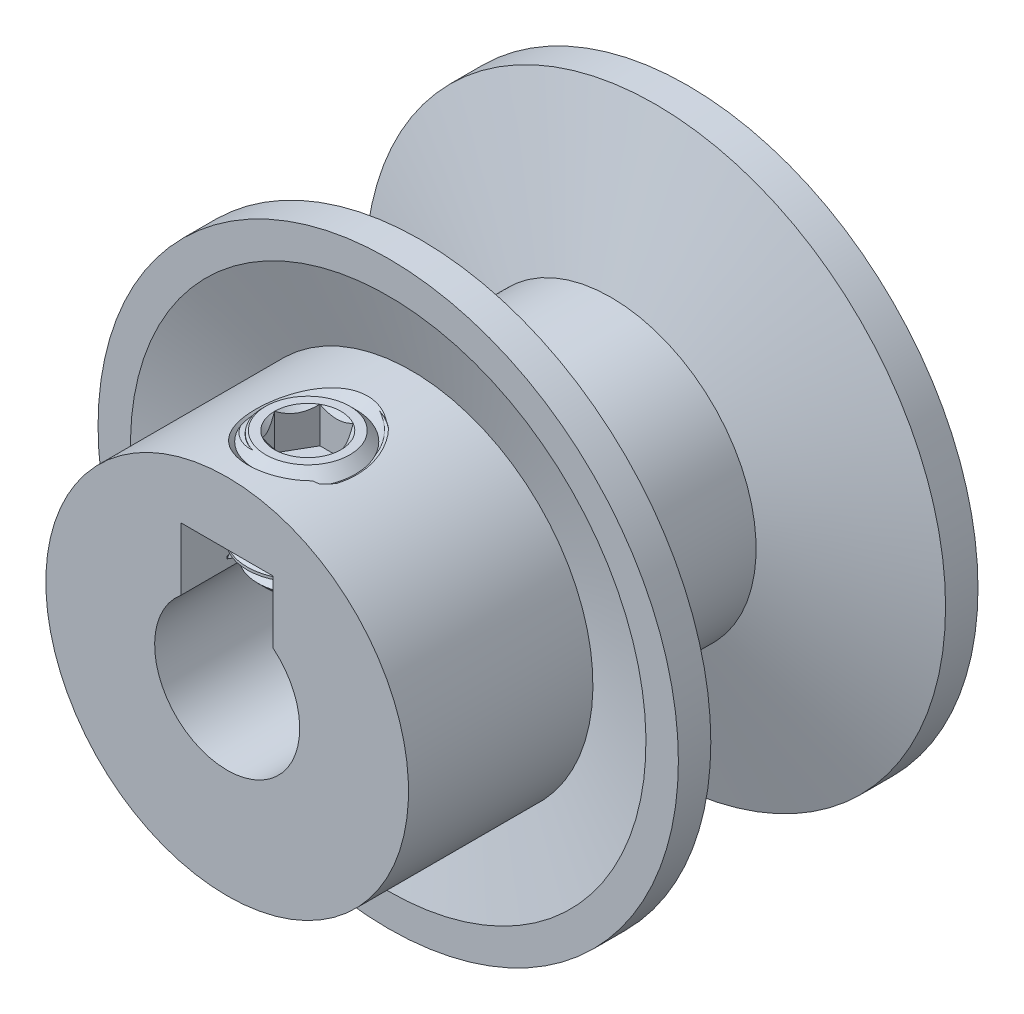
SolidWorks part; units mm, degrees
ref_plane "Front Plane" through (0, 0, 0) normal (0, 0, 1) x (1, 0, 0)
ref_plane "Top Plane" through (0, 0, 0) normal (0, 1, 0) x (1, 0, 0)
ref_plane "Right Plane" through (0, 0, 0) normal (1, 0, 0) x (0, 0, -1)
sketch "Sketch1" plane through (0, 0, 0) normal (1, 0, 0) x (0, 0, -1)
  line L0 (-21.4249, 0) -> (10.3251, 0) construction
  line L1 (-8.0899, 20) -> (8.0899, 20) construction
  line L2 (8.0899, 20) -> (10.3251, 20)
  line L5 (-10.3251, 20) -> (10.3251, 20) construction
  line L7 (-10.3251, 0) -> (-10.3251, 12.5)
  line L9 (-10.3251, 17.7648) -> (-8.7155, 12.5)
  line L13 (-8.0899, 20) -> (-5.0326, 10)
  line L14 (-5.0326, 10) -> (5.0326, 10)
  line L15 (5.0326, 10) -> (8.0899, 20)
  line L16 (10.3251, 5) -> (-21.4249, 5) construction
  line L17 (0, 20) -> (0, 0) construction
  line L18 (-8.0899, 20) -> (-10.3251, 20)
  line L20 (-21.4249, 0) -> (-21.4249, 5) construction
  line L22 (5.109, 10.25) -> (-5.109, 10.25) construction
  line L23 (10.3251, 20) -> (10.3251, 0) construction
  line L24 (-8.7155, 12.5) -> (-10.3251, 12.5)
  line L26 (-10.3251, 0) -> (6.3564, 0)
  line L27 (6.3564, 6.15) -> (6.7741, 6.15)
  line L28 (6.7741, 6.15) -> (10.3251, 17.7648)
  line L29 (-10.3251, 17.7648) -> (-10.3251, 20)
  line L31 (10.3251, 17.7648) -> (10.3251, 20)
  line L32 (6.3564, 0) -> (6.3564, 6.15)
  line L33 (10.3251, 20) -> (10.3251, 0) construction
  line L34 (-21.4249, 12.5) -> (-21.4249, -12.5) construction
  line L35 (5.8581, 12.7) -> (-5.8581, 12.7) construction
  point P16 (0, 10)
  point P38 (-10.3124, 0)
revolve "Revolve1" add sketch "Sketch1" angle 360 about L0
sketch "Sketch2" plane through (0, 0, 0) normal (1, 0, 0) x (0, 0, -1)
  line L0 (10.3251, 0) -> (-21.4249, 0) construction
  line L3 (-10.3124, 0) -> (-10.3124, 12.5)
  line L4 (-10.3124, 12.5) -> (-21.4249, 12.5)
  line L5 (-21.4249, 12.5) -> (-21.4249, 0)
  line L8 (-21.4249, 0) -> (-10.3124, 0)
revolve "Revolve2" add sketch "Sketch2" angle 360 about L0
sketch "Sketch3" plane through (0, 0, 21.4249) normal (0, 0, -1) x (-1, 0, 0)
  line L0 (-3.175, 5) -> (3.175, 5) construction
  line L1 (-3.175, 8.175) -> (3.175, 8.175) construction
  line L2 (-3.175, 8.175) -> (-3.175, 1.825) construction
  line L3 (-3.175, 1.825) -> (3.175, 1.825) construction
  line L4 (3.175, 8.175) -> (3.175, 1.825) construction
  circle A0 centre (0, 0) radius 5
  circle A1 centre (0, 0) radius 10.25 construction
  circle A2 centre (0, 0) radius 12.7 construction
  dimension "Keyway Wd." = 6.35
  dimension "Keyway Dp." = 3.175
extrude "Cut-Extrude1" cut sketch "Sketch3" along normal up to vertex (31.75 mm away) up to point (0, 0, -10.3251)
sketch "Sketch4" plane through (0, 0, 21.4249) normal (0, 0, -1) x (-1, 0, 0)
  line L0 (-3.175, 8.175) -> (-3.175, 1.825) construction
  line L1 (-3.175, 8.175) -> (3.175, 8.175) construction
  line L2 (3.175, 8.175) -> (3.175, 1.825) construction
  line L3 (-3.175, 1.825) -> (3.175, 1.825) construction
  line L4 (-3.175, 8.175) -> (-3.175, 1.825)
  line L5 (-3.175, 8.175) -> (3.175, 8.175)
  line L6 (3.175, 8.175) -> (3.175, 1.825)
  line L7 (-3.175, 1.825) -> (3.175, 1.825)
  line L8 (-3.175, 5) -> (3.175, 5) construction
  line L9 (-3.175, 5) -> (3.175, 5) construction
extrude "Cut-Extrude2" cut sketch "Sketch4" along normal up to vertex (31.75 mm away) up to point (0, 0, -10.3251)
ref_plane "Plane1" through (0, 12.5, 0) normal (0, 1, 0) x (-1, 0, 0)
sketch "Sketch5" plane through (0, 12.5, 0) normal (0, 1, 0) x (-1, 0, 0)
  line L0 (0, 10.3124) -> (0, 21.4249) construction
  line L7 (0, 19.8374) -> (0, 18.4263) construction
  circle A0 centre (0, 15.8686) radius 3.9688 construction
  circle A1 centre (0, 15.8686) radius 3.0868
  dimension "D3" = 0.8819
extrude "Cut-Extrude3" cut sketch "Sketch5" against normal up to surface (12.5 mm away) up to plane "Top Plane"
sketch "Sketch6" plane through (0, 12.5, 0) normal (0, 1, 0) x (-1, 0, 0)
  circle A0 centre (0, 15.8686) radius 3.9688 construction
  circle A1 centre (0, 15.8686) radius 3.9688
  point P3 (0, 19.8374)
curve "Helix/Spiral1" pitch 1.4111 height 13.9111 radius 3.9688 centre (0, 12.5, 15.8686) axis (0, -1, 0) start towards (0, 0, 1)
sketch "Sketch7" plane through (0, 0, 0) normal (1, 0, 0) x (0, 0, -1)
  line L0 (-18.7681, 13.9111) -> (-18.7681, 12.5) construction
  line L1 (-18.7681, 12.5) -> (-19.9902, 13.2056) construction
  line L2 (-19.9902, 13.2056) -> (-18.7681, 13.9111) construction
  line L3 (-18.7681, 12.5) -> (-19.8374, 12.5) construction
  line L4 (-19.8374, 12.5) -> (-19.8374, 13.1174) construction
  line L5 (-19.8374, 13.1174) -> (-19.8374, 13.2937) construction
  line L6 (-18.9209, 12.5882) -> (-18.9209, 13.8229) construction
  line L7 (-19.9902, 13.2056) -> (-19.8374, 13.2056) construction
  line L8 (-18.9209, 13.2056) -> (-18.7681, 13.2056) construction
  line L9 (-18.8445, 13.867) -> (-18.8445, 12.5441)
  line L10 (-18.8445, 12.5441) -> (-19.8374, 13.1174)
  line L11 (-19.8374, 13.1174) -> (-19.8374, 13.2937)
  line L12 (-19.8374, 13.2937) -> (-18.8445, 13.867)
  point P16 (-18.8445, 13.2056)
  dimension "D1" = 1.4111
  dimension "D2" = 0.1764
sweep "Cut-Sweep1" cut profiles "Sketch7" path "Helix/Spiral1" align with end faces yes
sketch "Sketch8" plane through (0, 12.5, 0) normal (0, 1, 0) x (-1, 0, 0)
  circle A0 centre (0, 15.8686) radius 4.1215
extrude "Cut-Extrude4" cut sketch "Sketch8" against normal through all draft 45
sketch "Sketch9" plane through (0, 0, 0) normal (1, 0, 0) x (0, 0, -1)
  line L0 (-15.8686, 12.5) -> (-15.8686, 4.5625) construction
  line L1 (-19.8374, 5.6318) -> (-19.8374, 11.4307)
  line L2 (-15.8686, 12.5) -> (-19.8374, 12.5) construction
  line L3 (-15.8686, 12.5) -> (-15.8686, 4.5625)
  line L4 (-15.8686, 4.5625) -> (-19.8374, 4.5625) construction
  line L5 (-19.8374, 12.5) -> (-19.8374, 4.5625) construction
  line L6 (-18.7681, 12.5) -> (-19.8374, 11.4307)
  line L7 (-19.8374, 5.6318) -> (-18.7681, 4.5625)
  line L8 (-18.7681, 12.5) -> (-15.8686, 12.5)
  line L9 (-18.7681, 4.5625) -> (-15.8686, 4.5625)
  line L10 (-10.3124, 12.5) -> (-21.4249, 12.5) construction
  line L11 (-18.7681, 12.5) -> (-19.8374, 12.5) construction
  line L12 (-19.8374, 12.5) -> (-19.8374, 11.4307) construction
revolve "Revolve3" add sketch "Sketch9" angle 360 about L0
sketch "Sketch10" plane through (0, 12.5, 0) normal (0, 1, 0) x (-1, 0, 0)
  circle A1 centre (0, 15.8686) radius 3.9688
  circle A2 centre (0, 15.8686) radius 3.9688
  dimension "D1" = 0
curve "Helix/Spiral2" pitch 1.4111 height 9.3486 turns 6.625
sketch "Sketch11" plane through (0, 0, 0) normal (1, 0, 0) x (0, 0, -1)
  line L0 (-19.9902, 13.2056) -> (-19.9902, 11.7944) construction
  line L1 (-19.9902, 11.7944) -> (-18.7681, 12.5) construction
  line L2 (-18.7681, 12.5) -> (-19.9902, 13.2056) construction
  line L4 (-18.9209, 12.5882) -> (-18.9209, 12.4118)
  line L5 (-18.9209, 12.4118) -> (-19.8374, 11.8826)
  line L6 (-19.8374, 11.8826) -> (-19.8374, 13.1174)
  line L7 (-19.8374, 13.1174) -> (-18.9209, 12.5882)
sweep "Cut-Sweep2" cut profiles "Sketch11" path "Helix/Spiral2" align with end faces yes
sketch "Sketch12" plane through (0, 12.5, 0) normal (0, 1, 0) x (1, 0, 0)
  line L1 (2.2914, -15.8687) -> (1.1457, -13.8843)
  line L2 (1.1457, -13.8843) -> (-1.1457, -13.8843)
  line L3 (-1.1457, -13.8843) -> (-2.2914, -15.8686)
  line L4 (-2.2914, -15.8686) -> (-1.1457, -17.853)
  line L5 (-1.1457, -17.853) -> (1.1457, -17.853)
  line L6 (1.1457, -17.853) -> (2.2914, -15.8687)
  circle A0 centre (0, -15.8687) radius 1.9844 construction
extrude "Cut-Extrude5" cut sketch "Sketch12" against normal blind 2.4805
sketch "Sketch13" plane through (0, 12.5, 0) normal (0, 1, 0) x (1, 0, 0)
  circle A0 centre (0, -15.8687) radius 2.2914
extrude "Cut-Extrude6" cut sketch "Sketch13" against normal through all draft 45
equation "\"D3@Sketch5\" = \"Set Screw Pitch@Sketch5\" * 5 / 8"
equation "\"D4@Helix/Spiral1\" = \"Set Screw Pitch@Sketch5\""
equation "\"D3@Helix/Spiral1\" = \"D4@Helix/Spiral1\" + ( \"Hub Dia.@Sketch1\" / 2 ) "
equation "\"D1@Sketch7\" = \"D4@Helix/Spiral1\""
equation "\"D2@Sketch7\" = \"D1@Sketch7\" / 8"
equation "\"Set Screw Hex@Sketch12\" = \"Set Screw Dia.@Sketch5\" / 2"
equation "\"D1@Cut-Extrude5\" = \"Set Screw Hex@Sketch12\" * 5 / 8"
equation "\"D4@Helix/Spiral2\" = \"D4@Helix/Spiral1\""
equation "\"D3@Helix/Spiral2\" = \"D4@Helix/Spiral1\" + \"Set Screw Lg.@Sketch9\""
